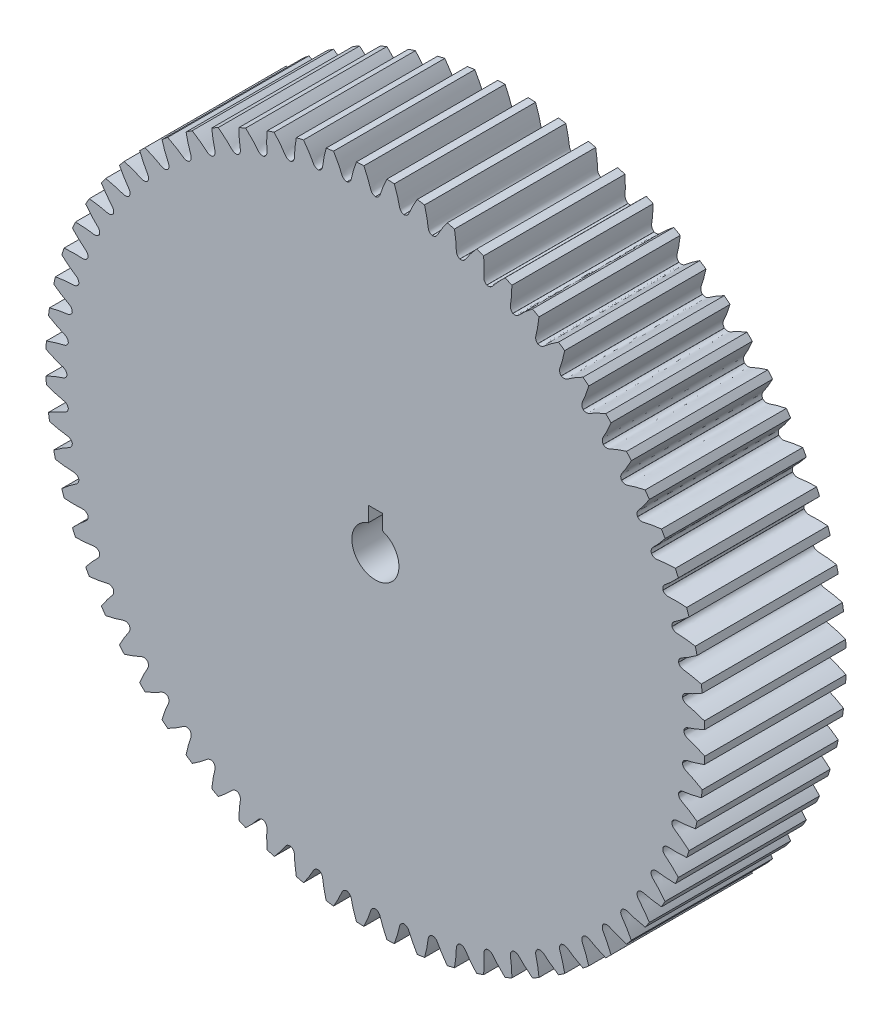
SolidWorks part; units mm, degrees
ref_plane "前视基准面" through (0, 0, 0) normal (0, 0, 1) x (1, 0, 0)
ref_plane "上视基准面" through (0, 0, 0) normal (0, 1, 0) x (1, 0, 0)
ref_plane "右视基准面" through (0, 0, 0) normal (1, 0, 0) x (0, 0, -1)
other "Configuration Table"
sketch "草图1" plane through (0, 0, 0) normal (0, 0, 1) x (1, 0, 0)
  circle A0 centre (0, 0) radius 70
extrude "凸台-拉伸1" add sketch "草图1" along normal blind 30
ref_axis "基准轴1" through (0, 0, -1.5) along (0, 0, 1)
sketch "草图2" plane through (0, 0, 0) normal (0, 0, 1) x (1, 0, 0)
  line L0 (0, 0) -> (0, 70) construction
  circle A0 centre (0, 0) radius 70 construction
  arc A1 (0.01, 65.4996) -> (-0.01, 65.4996) centre (0, 0) ccw
  arc A2 (9.0672, 79.2707) -> (-9.0672, 79.2707) centre (0, 0) ccw
  spline S0 degree 3 poles (0.01, 65.4996) (0.8576, 65.6646) (1.0073, 66.4058) (1.295, 67.2393) (1.4409, 67.6458) (1.6048, 68.0725) (1.7866, 68.5198) (1.9875, 68.9868) (2.2082, 69.4729) (2.4496, 69.9776) (2.7125, 70.5002) (2.9978, 71.04) (3.3062, 71.5964) (3.6385, 72.1686) (3.9955, 72.7559) (4.3778, 73.3575) (4.7862, 73.9727) (5.2214, 74.6006) (5.6841, 75.2403) (6.1748, 75.8911) (6.6943, 76.552) (7.243, 77.2222) (8.0256, 78.1399) (8.6418, 78.8196) (9.0672, 79.2707) knots 0 0 0 0 0.108777 0.133168 0.159093 0.186554 0.21555 0.246082 0.278148 0.31175 0.346887 0.383559 0.421766 0.461509 0.502786 0.545599 0.589947 0.635831 0.683249 0.732203 0.782692 0.834716 0.888276 1 1 1 1
  spline S1 degree 3 poles (-0.01, 65.4996) (-0.8576, 65.6646) (-1.0073, 66.4058) (-1.295, 67.2393) (-1.4409, 67.6458) (-1.6048, 68.0725) (-1.7866, 68.5198) (-1.9875, 68.9868) (-2.2082, 69.4729) (-2.4496, 69.9776) (-2.7125, 70.5002) (-2.9978, 71.04) (-3.3062, 71.5964) (-3.6385, 72.1686) (-3.9955, 72.7559) (-4.3778, 73.3575) (-4.7862, 73.9727) (-5.2214, 74.6006) (-5.6841, 75.2403) (-6.1748, 75.8911) (-6.6943, 76.552) (-7.243, 77.2222) (-8.0256, 78.1399) (-8.6418, 78.8196) (-9.0672, 79.2707) knots 0 0 0 0 0.108777 0.133168 0.159093 0.186554 0.21555 0.246082 0.278148 0.31175 0.346887 0.383559 0.421766 0.461509 0.502786 0.545599 0.589947 0.635831 0.683249 0.732203 0.782692 0.834716 0.888276 1 1 1 1
extrude "切除-拉伸1" cut sketch "草图2" along normal through all
pattern_circular "阵列(圆周)1" count 68 every 5.294 about axis through (0, 0, -1.5) along (0, 0, 1) of "切除-拉伸1"
sketch "草图3" plane through (0, 0, 0) normal (0, 0, 1) x (1, 0, 0)
  circle A0 centre (0, 0) radius 68 construction
  dimension "Dn" = 136
sketch "草图4" plane through (0, 0, 30) normal (0, 0, 1) x (1, 0, 0)
  line L0 (0, 0) -> (-5, 0)
  line L1 (-5, 0) -> (-5, 20)
  line L2 (-5, 20) -> (5, 20)
  line L3 (5, 20) -> (5, 0)
  line L4 (5, 0) -> (0, 0)
  circle A0 centre (0, 0) radius 15
extrude "切除-拉伸2" cut sketch "草图4" against normal through all contours L3 A0 L1 L0 L4 | A0 L3 L2 L1 | L1 A0 L3 L4 L0 region at (0, -1.9356, 30) region at (0, 7.3609, 30) region at (0, 17.3526, 30)
sketch "草图5" plane through (0, 0, 30) normal (0, 0, 1) x (1, 0, 0)
  circle A0 centre (0, 0) radius 27.4637
extrude "凸台-拉伸2" add sketch "草图5" against normal through all
sketch "草图6" plane through (0, 0, 30) normal (0, 0, 1) x (1, 0, 0)
  line L0 (0, 0) -> (-1.5, 0)
  line L1 (-1.5, 0) -> (-1.5, 8)
  line L2 (-1.5, 8) -> (1.5, 8)
  line L3 (1.5, 8) -> (1.5, 0)
  line L4 (1.5, 0) -> (0, 0)
  circle A1 centre (0, 0) radius 5
extrude "切除-拉伸3" cut sketch "草图6" against normal through all contours L3 A1 L1 L0 L4 | L1 A1 L3 L4 L0 | A1 L3 L2 L1 region at (0, -0.5704, 30) region at (0, 2.4625, 30) region at (0, 6.4612, 30)
